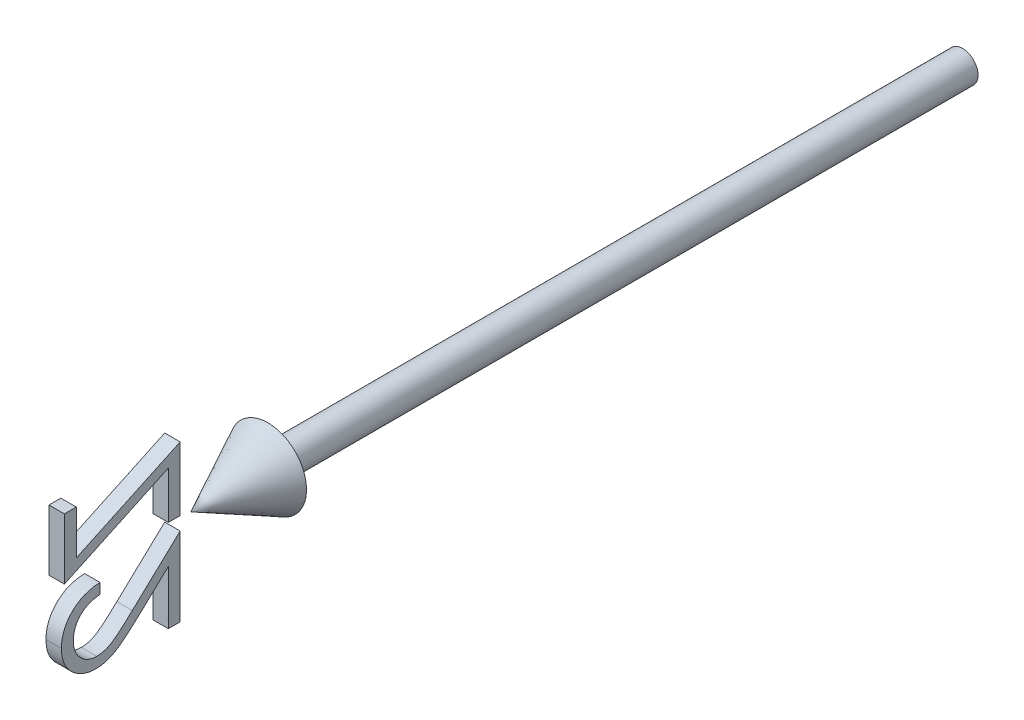
SolidWorks part; units mm, degrees
ref_plane "Front Plane" through (0, 0, 0) normal (0, 0, 1) x (1, 0, 0)
ref_plane "Top Plane" through (0, 0, 0) normal (0, 1, 0) x (1, 0, 0)
ref_plane "Right Plane" through (0, 0, 0) normal (1, 0, 0) x (0, 0, -1)
sketch "Sketch2" plane through (0, 0, 0) normal (0, 1, 0) x (1, 0, 0)
  line L0 (0, 41.95) -> (0, -114.4521) construction
  line L1 (-36.8894, 0) -> (41.4965, 0) construction
  line L2 (0, -100) -> (5, -90)
  line L3 (5, -90) -> (2, -90)
  line L4 (2, -90) -> (2, 0)
  line L5 (2, 0) -> (0, 0)
  line L6 (0, 0) -> (0, -100)
  dimension "D1" = 100
  dimension "D2" = 2
  dimension "D3" = 10
  dimension "D4" = 5
revolve "Revolve1" add sketch "Sketch2" angle 360 about L0
sketch "Sketch3" plane through (0, 0, 0) normal (1, 0, 0) x (0, -1, 0)
  line L0 (0, -101.5706) -> (0, -127.8138) construction
  line L1 (-10.1124, -102.3675) -> (14.1256, -102.3675) construction
  text T0 "Z2" font "Century Gothic" height 15
extrude "Boss-Extrude1" add sketch "Sketch3" against normal blind 1 and the other way blind 1 separate body
equation "\"frame_arrow_length\"=100"
equation "\"D1@Sketch2\"=\"frame_arrow_length\""
equation "\"frame_arrow_odA\"=4"
equation "\"D2@Sketch2\"=\"frame_arrow_odA\"/2"
equation "\"frame_arrow_head_od\"=5"
equation "\"D4@Sketch2\"=\"frame_arrow_head_od\""
equation "\"frame_arrow_head_length\"=10"
equation "\"D3@Sketch2\"=\"frame_arrow_head_length\""
equation "\"tvarobot_theta1\"=30"
equation "\"link0_ringA_odA\"= 40"
equation "\"link0_ringA_odB\"= 25"
equation "\"link0_ringA_id\"= 20"
equation "\"link0_ringA_thickness\"= (\"link0_ringA_odB\" - \"link0_ringA_id\")/2"
equation "\"link0_ringA_height\"= 3"
equation "\"link0_ringA_heightA\"= 1.5"
equation "\"link0_ringA_heightB\"=\"link0_ringA_height\"-\"link0_ringA_heightA\""
equation "\"link0_ringB_odA\"= 40"
equation "\"link0_ringB_odB\"= 29"
equation "\"link0_ringB_id\"= \"link0_shaftA_bearing_id\"+1"
equation "\"link0_ringB_thickness\"= (\"link0_ringB_odB\" - \"link0_ringB_id\")/2"
equation "\"link0_ringB_height\"= 3"
equation "\"link0_ringB_heightA\"= 1.5"
equation "\"link0_ringB_heightB\"=\"link0_ringB_height\"-\"link0_ringB_heightA\""
equation "\"link0_shaftA_bearing_od\"=27"
equation "\"link0_shaftA_bearing_id\"=20"
equation "\"link0_shaftA_thrust_bearing_od\"=35"
equation "\"link0_shaftA_thrust_bearing_id\"=20.04"
equation "\"link0_shaftA_retaining_ring_id\"=18.5"
equation "\"link0_shaftA_retaining_ring_groove_width\"=1.5"
equation "\"link0_shaftA_spline_length\"=8.0"
equation "\"link0_shaftA_spline_depth\"=1.0"
equation "\"link0_shaftA_spline_width\"=4.0"
equation "\"link0_shaftA_odA\"=\"link0_shaftA_bearing_id\""
equation "\"link0_shaftA_odB\"=35"
equation "\"link0_shaftA_odC\"=\"link0_shaftA_bearing_id\""
equation "\"link0_shaftA_odD\"=\"link0_shaftA_odC\"-2*\"link0_shaftA_spline_depth\""
equation "\"link0_shaftA_odE\"=\"link0_shaftA_bearing_id\""
equation "\"link0_shaftA_odF\"=\"link0_shaftA_odE\"-2*\"link0_shaftA_spline_depth\""
equation "\"link0_shaftA_idA\"=10"
equation "\"link0_shaftA_idB\"=6"
equation "\"link0_shaftA_length\"=39.5"
equation "\"link0_shaftA_lengthA\"=8.0"
equation "\"link0_shaftA_lengthB\"=12.0"
equation "\"link0_shaftA_lengthC\"=35.0"
equation "\"link0_shaftA_lengthD\"=39.0"
equation "\"link0_shaftA_lengthE\"=\"link0_shaftA_length\"-\"link0_shaftA_lengthD\""
equation "\"link0_shaftA_offsetX\"=11"
equation "\"link0_shaftA_offsetY\"=0"
equation "\"link0_shaftA_bolt_pattern_dia\"=14"
equation "\"link0_motor_center_dist\"=26"
equation "\"link0_46t_pulley_spline_length\"=8"
equation "\"link0_46t_pulley_spline_depth\"=\"link0_shaftA_spline_depth\"*1.025"
equation "\"link0_46t_pulley_spline_width\"=\"link0_shaftA_spline_width\"*1.05"
equation "\"link0_46t_pulley_idA\"=\"link0_shaftA_bearing_id\"*1.025"
equation "\"link0_46t_pulley_idB\"=\"link0_46t_pulley_idA\"-2*\"link0_46t_pulley_spline_depth\""
equation "\"link0_shaftB_spline_length\"=10"
equation "\"link0_shaftB_spline_depth\"=1.0"
equation "\"link0_shaftB_spline_width\"=1.25"
equation "\"link0_shaftB_length\"=7"
equation "\"link0_shaftB_lengthA\"=1.5"
equation "\"link0_shaftB_lengthB\"=2.75"
equation "\"link0_shaftB_odA\"=32"
equation "\"link0_shaftB_odB\"=22"
equation "\"link0_shaftB_odC\"=20"
equation "\"link0_shaftB_idA\"=10"
equation "\"link0_shaftB_bolt_diameter\"=19"
equation "\"link0_shaftB_bearing_od\"=27"
equation "\"link0_shaftB_bearing_id\"=20"
equation "\"link0_motor_length\"=46.5"
equation "\"link0_motor_width\"=28.5"
equation "\"link0_motor_height\"=34"
equation "\"link0_motor_offset\"=8"
equation "\"link0_shellA_thickness\"=2.5"
equation "\"link0_shellB_thickness\"=\"link0_shellA_thickness\""
equation "\"link0_plateA_shellA_height\"=48"
equation "\"link0_shellA_width\" =\"link0_plateA_width\""
equation "\"link0_shellA_height\" = \"link0_plateA_shellA_height\"-\"link0_plateA_height\""
equation "\"link0_shellA_length\" = \"link0_plateA_lengthB\" "
equation "\"link0_shellB_length\"=\"link0_shellA_length\""
equation "\"link0_shellA_radius\" = 0.375*25.4"
equation "\"link0_shellA_radiusA\"= \"link0_plateA_radiusA\""
equation "\"link0_shellA_radiusB\"= \"link0_plateA_radiusB\""
equation "\"link0_shellA_radiusC\"= 3"
equation "\"link0_postA_height\"=7"
equation "\"link0_postA_width\"=16"
equation "\"link0_postA_length\"=20"
equation "\"link0_postA_posX\"=22"
equation "\"link0_postA_posY\"=17.5"
equation "\"link0_postA_pocket_width\"=6.0"
equation "\"link0_postA_pocket_length\"=2.5"
equation "\"link0_postA_pocket_depth\"=9"
equation "\"link0_postA_pocket_posZ\"=10"
equation "\"link0_postB_height\"=7"
equation "\"link0_postB_width\"=16"
equation "\"link0_postB_length\"=20"
equation "\"link0_postB_posX\"=22"
equation "\"link0_postB_posY\"=17.5"
equation "\"link0_postB_id\"=3.0"
equation "\"link0_postB_pocket_width\"=6.0"
equation "\"link0_postB_pocket_length\"=2.5"
equation "\"link0_postB_pocket_depth\"=9"
equation "\"link0_postB_pocket_posZ\"=10"
equation "\"link0_postC_height\"=7"
equation "\"link0_postC_width\"=16"
equation "\"link0_postC_length\"=20"
equation "\"link0_postC_posX\"=22"
equation "\"link0_postC_posY\"=17.5"
equation "\"link0_postC_id\"=3.0"
equation "\"link0_postC_pocket_width\"=6.0"
equation "\"link0_postC_pocket_length\"=2.5"
equation "\"link0_postC_pocket_depth\"=9"
equation "\"link0_postC_pocket_posZ\"=10"
equation "\"link0_postD_height\"=7"
equation "\"link0_postD_width\"=16"
equation "\"link0_postD_length\"=20"
equation "\"link0_postD_posX\"=22"
equation "\"link0_postD_posY\"=17.5"
equation "\"link0_postD_id\"=3.0"
equation "\"link0_postD_pocket_width\"=6.0"
equation "\"link0_postD_pocket_length\"=3.0"
equation "\"link0_postD_pocket_depth\"=9"
equation "\"link0_postD_pocket_posZ\"=10"
equation "\"link0_postE_height\"=5"
equation "\"link0_postE_width\"=16"
equation "\"link0_postE_length\"=\"link0_plateE_lengthA\"-\"link0_lip_height\""
equation "\"link0_postE_posZ\"=22"
equation "\"link0_postE_posX\"=17.5"
equation "\"link0_postE_posY\"=22"
equation "\"link0_postE_id\"=3.0"
equation "\"link0_postE_cbore_id\"=6.5"
equation "\"link0_postE_hole_id\"=3"
equation "\"link0_postF_posZ\"=22"
equation "\"link0_postF_posX\"=17.5"
equation "\"link0_postF_posY\"=\"link0_plateB_lengthA\"+4"
equation "\"link0_postF_id\"=3.0"
equation "\"link0_postF_cbore_id\"=6.5"
equation "\"link0_postF_hole_id\"=3"
equation "\"link0_postG_posZ\"=22"
equation "\"link0_postG_posX\"=17.5"
equation "\"link0_postG_posY\"=\"link0_plateB_lengthA\"+12"
equation "\"link0_postG_id\"=3.0"
equation "\"link0_postG_cbore_id\"=6.5"
equation "\"link0_postG_hole_id\"=3"
equation "\"link0_postHIJ_posY\"=6"
equation "\"link0_postH_posX\"=28"
equation "\"link0_postH_posY\"=20"
equation "\"link0_postH_posZ\"=20"
equation "\"link0_postH_length\"=10"
equation "\"link0_postI_posX\"=28"
equation "\"link0_postI_posY\"=20"
equation "\"link0_postI_posZ\"=135"
equation "\"link0_postI_length\"=10"
equation "\"link0_postJ_posX\"=28"
equation "\"link0_postJ_posY\"=20"
equation "\"link0_postJ_posZ\"=175"
equation "\"link0_postJ_length\"=10"
equation "\"link0_postK_posX\"=28"
equation "\"link0_postK_posY\"=20"
equation "\"link0_postK_posZ\"=175"
equation "\"link0_postK_length\"=10"
equation "\"link0_postL_posX\"=28"
equation "\"link0_postL_posY\"=20"
equation "\"link0_postL_posZ\"=135"
equation "\"link0_postL_length\"=10"
equation "\"link0_postM_posX\"=28"
equation "\"link0_postM_posY\"=20"
equation "\"link0_postM_posZ\"=35"
equation "\"link0_postM_length\"=10"
equation "\"link0_plateA_lengthA\"=30"
equation "\"link0_plateA_lengthB\"=150"
equation "\"link0_plateA_lengthC\"=30"
equation "\"link0_plateA_length\"=\"link0_plateA_lengthA\"+\"link0_plateA_lengthB\"+\"link0_plateA_lengthC\""
equation "\"link0_plateA_width\"=  68"
equation "\"link0_plateA_height\"= \"link0_plateA_radiusA\""
equation "\"link0_plateA_thickness\"=\"link0_shellA_thickness\""
equation "\"link0_plateA_radius\"= 9.5"
equation "\"link0_plateA_radiusA\"= 18"
equation "\"link0_plateA_radiusB\"= 18"
equation "\"link0_plateA_radiusC\"= 3"
equation "\"link0_plateB_length\"= 40"
equation "\"link0_plateB_width\"= \"link0_plateA_width\"*1.005"
equation "\"link0_plateB_height\"= \"link0_plateA_shellA_height\"*1.005"
equation "\"link0_plateB_lengthA\"=\"link0_lip_height\"+\"link0_plateD_thickness\"+\"link0_motor_mount_thickness\""
equation "\"link0_plateB_lengthB\"=\"link0_plateB_height\"-\"link0_plateB_lengthA\""
equation "\"link0_plateB_radiusA\"= \"link0_plateA_radiusA\""
equation "\"link0_plateB_radiusB\"= \"link0_plateA_radiusB\""
equation "\"link0_plateB_radiusC\"= 3"
equation "\"link0_plateB_idA\"=\"link0_shaftA_odC\"+1"
equation "\"link0_plateB_idB\"=\"link0_shaftA_bearing_od\"-2"
equation "\"link0_plateB_idC\"=\"link0_shaftA_bearing_od\"*1.005"
equation "\"link0_plateB_idD\"=\"link0_shaftA_thrust_bearing_od\"+1 "
equation "\"link0_plateB_depthA\"=1.0"
equation "\"link0_plateB_depthB\"=2.0"
equation "\"link0_plateB_depthC\"=8"
equation "\"link0_plateB_depthD\"=\"link0_plateB_length\"-\"link0_lip_height\"-\"link0_plateD_thickness\" "
equation "\"link0_plateC_length\"=\"link0_plateB_length\""
equation "\"link0_plateC_width\"= \"link0_plateB_width\""
equation "\"link0_plateC_height\"= .1*25.4"
equation "\"link0_plateA_hole_od\" = 0.1*25.4"
equation "\"link0_plateA_hole_delx\" = 0.5*25.4"
equation "\"link0_plateA_hole_delz\" = 0.75*25.4"
equation "\"link0_plateA_hole_offx\" = 0.0*25.4"
equation "\"link0_plateA_hole_offz\" = \"link0_plateA_length\"/2"
equation "\"link0_plateB_hole_od\" = 0.1*25.4"
equation "\"link0_plateB_hole_delx\"= 0.75*25.4"
equation "\"link0_plateB_hole_delz\"= 0.75*25.4"
equation "\"link0_plateB_hole_offx\"= 0.0*25.4"
equation "\"link0_plateB_hole_offz\"= 0.0*25.4"
equation "\"link0_plateC_hole_od\"= 0.1*25.4"
equation "\"link0_plateC_hole_delx\"= 0.75*25.4"
equation "\"link0_plateC_hole_delz\"= 0.75*25.4"
equation "\"link0_plateC_hole_offx\"= 0.0*25.4"
equation "\"link0_plateC_hole_offz\"= 0.0*25.4"
equation "\"link0_plateD_height\"=\"link0_plateB_height\"-2*\"link0_shellA_thickness\""
equation "\"link0_plateD_width\"=\"link0_plateB_width\"-2*\"link0_shellA_thickness\""
equation "\"link0_plateD_thickness\"=10"
equation "\"link0_plateD_radiusA\"=\"link0_plateB_radiusA\"-\"link0_shellA_thickness\""
equation "\"link0_plateD_odA\"= .375*25.4"
equation "\"link0_plateD_odB\"= .375*25.4"
equation "\"link0_plateD_bearing_id\"=20"
equation "\"link0_plateD_bearing_od\"=27"
equation "\"link0_plateE_radiusA\"=\"link0_plateA_radiusA\""
equation "\"link0_plateE_radiusB\"=\"link0_plateA_radiusB\""
equation "\"link0_plateE_radiusC\"=8.0"
equation "\"link0_plateE_length\"=30"
equation "\"link0_plateE_lengthA\"=16"
equation "\"link0_plateE_height\"=\"link0_plateB_height\""
equation "\"link0_plateE_width\"=\"link0_plateB_width\""
equation "\"link0_plateE_odA\"=\"gantry_coupler_id\"*0.99"
equation "\"link0_plateE_idA\"=\"link0_plateE_odA\"-20.0"
equation "\"link0_plateE_spline_depth\"=\"link0_poleA_spline_depth\"*1.05"
equation "\"link0_plateE_spline_width\"=\"link0_poleA_spline_width\"*1.075"
equation "\"link0_plateE_spline_length\"=\"link0_poleA_spline_length\""
equation "\"link0_plateE_coupler_length\"=46"
equation "\"link0_lip_height\"=5.0"
equation "\"link0_lip_thickness\"=2.0"
equation "\"link0_motor_mount_thickness\"=8.0"
equation "\"link0_motor_mount_idA\"=22"
equation "\"link0_motor_mount_idB\"=\"link0_shaftB_bearing_od\"*1.005"
equation "\"link0_motor_mount_idC\"=\"link0_shaftB_bearing_od\"-2"
equation "\"link0_motor_mount_depthA\"=5.5"
equation "\"link0_motor_mount_height\"=\"link0_plateD_height\""
equation "\"link0_motor_mount_width\"=\"link0_plateD_width\""
equation "\"link0_motor_mountL_height\"=36"
equation "\"link0_motor_mountL_heightA\"=12"
equation "\"link0_motor_mountL_length\"=50"
equation "\"link0_motor_mountL_lengthA\"=36"
equation "\"gantry_coupler_od\"=25.4*2.0"
equation "\"gantry_coupler_id\"=1.645*25.4"
equation "\"gantry_coupler_offsetX\"=\"link0_plateE_width\"/2"
equation "\"link0_poleA_odA\"=20"
equation "\"link0_poleA_odB\"=36"
equation "\"link0_poleA_idA\"=\"link0_poleA_odA\"-2*\"link0_poleA_thickness\""
equation "\"link0_poleA_idB\"=(\"link0_plateE_idA\"/2+1.5*\"link0_lip_thickness\")*1.04"
equation "\"link0_poleA_thickness\"=3.5"
equation "\"link0_poleA_length\"=100"
equation "\"link0_poleA_lengthA\"=18.5"
equation "\"link0_poleA_lengthB\"=80"
equation "\"link0_poleA_gasket_thickness\"=1.5"
equation "\"link0_poleA_spline_depth\"=1.0"
equation "\"link0_poleA_spline_width\"=4.0"
equation "\"link0_poleA_spline_length\"=10.0"
equation "\"link1_plateB_length\"=30"
equation "\"link1_lip_height\"=\"link0_lip_height\""
equation "\"link0_tension_plateA_width\"=12"
equation "\"link0_tension_plateA_lengthA\"=10.5"
equation "\"link0_tension_plateB_width\"=\"link0_tension_plateA_width\""
equation "\"link0_tension_plateB_lengthA\"=\"link0_tension_plateA_lengthA\""
equation "\"link0_tension_wheelA_posZ\"=7"
equation "\"link0_tension_wheelA_posX\"=\"link0_plateD_height\"/2-\"link0_tension_plateA_lengthA\""
equation "\"link0_m2_clear_hole_id\"=2.35"
equation "\"link0_m2_insert_hole_id\"=2.5"
equation "\"link0_m2_tap_hole_id\"=1.75"
equation "\"link0_m2_nut_socket_width\"=4.25"
equation "\"link0_m2_nut_socket_depth\"=2.5"
equation "\"link0_m2_cbore_id\"=3.75"
equation "\"link0_m2_cbore_depth\"=7"
equation "\"link0_m2_5_clear_hole_id\"=2.75"
equation "\"link0_m2_5_insert_hole_id\"=2.75"
equation "\"link0_m2_5_tap_hole_id\"=2.25"
equation "\"link0_m2_5_nut_socket_width\"=5.25"
equation "\"link0_m2_5_nut_socket_depth\"=2.5"
equation "\"link0_m2_5_cbore_id\"=4.75"
equation "\"link0_m2_5_cbore_depth\"=2.5"
equation "\"link0_m2_5_insert_access_length\"=6.0"
equation "\"link0_m2_5_insert_access_width\"=3.0"
equation "\"link0_m3_clear_hole_id\"=3.25"
equation "\"link0_m3_insert_hole_id\"=3"
equation "\"link0_m3_tap_hole_id\"=2.75"
equation "\"link0_m3_nut_socket_width\"=5.75"
equation "\"link0_m3_nut_socket_depth\"=4.0"
equation "\"link0_m3_cbore_id\"=5.75"
equation "\"link0_m3_cbore_depth\"=3.5"
equation "\"link0_m3_insert_access_length\"=4.5"
equation "\"link0_m3_insert_access_width\"=3.5"
equation "\"link0_rpi_mount_height\"=6"
equation "\"link0_rpi_mount_width\"=49"
equation "\"link0_rpi_mount_length\"=58"
equation "\"link0_rpi_mount_post_od\"=6"
equation "\"link0_rpi_mount_posZ\"=72"
equation "\"link0_rpi_mount_posX\"=11.5"
equation "\"link0_mcu_mount_height\"=5"
equation "\"link0_mcu_mount_width\"=49"
equation "\"link0_mcu_mount_length\"=58"
equation "\"link0_mcu_mount_post_od\"=6"
equation "\"link0_mcu_mount_posZ\"=164"
equation "\"link0_mcu_mount_posX\"=4"
equation "\"link0_pwr_mount_height\"=4"
equation "\"link0_pwr_mount_width\"=15.75"
equation "\"link0_pwr_mount_length\"=75.75"
equation "\"link0_pwr_mount_post_od\"=6"
equation "\"link0_pwr_mount_posZ\"=75"
equation "\"link0_pwr_mount_posX\"=16"
equation "\"link0_pwr_board_height\"=6"
equation "\"link0_pwr_board_width\"=21"
equation "\"link0_pwr_board_length\"=80"
